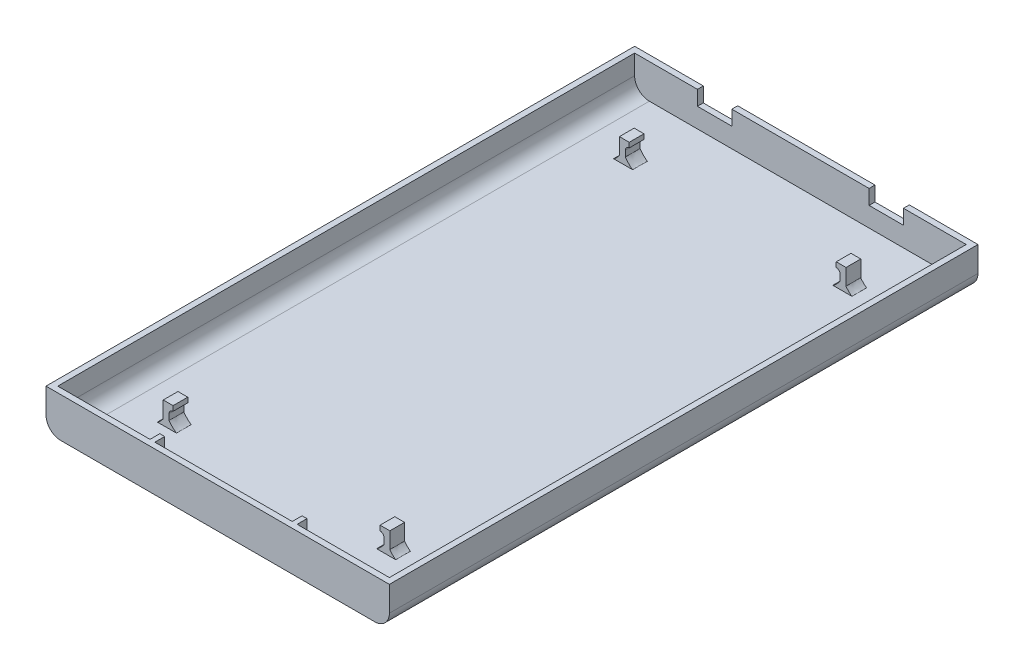
SolidWorks part; units mm, degrees
ref_plane "Front Plane" through (0, 0, 0) normal (0, 0, 1) x (1, 0, 0)
ref_plane "Top Plane" through (0, 0, 0) normal (0, 1, 0) x (1, 0, 0)
ref_plane "Right Plane" through (0, 0, 0) normal (1, 0, 0) x (0, 0, -1)
sketch "Sketch1" plane through (0, 0, 0) normal (0, 1, 0) x (1, 0, 0)
  line L1 (0, 0) -> (70, 0)
  line L2 (0, 0) -> (0, -120)
  line L3 (0, -120) -> (70, -120)
  line L4 (70, 0) -> (70, -120)
  dimension "D1" = 70
  dimension "D2" = 120
extrude "Boss-Extrude1" add sketch "Sketch1" along normal blind 1.1
sketch "Sketch2" plane through (0, 1.1, 0) normal (0, 1, 0) x (1, 0, 0)
  line L0 (70, -120) -> (70, 0) construction
  line L1 (0, -120) -> (70, -120)
  line L2 (0, -120) -> (0, 0)
  line L3 (0, 0) -> (70, 0)
  line L4 (70, -120) -> (70, 0)
  line L5 (1.2, -118.8) -> (1.2, -1.2)
  line L6 (1.2, -1.2) -> (68.8, -1.2)
  line L7 (68.8, -118.8) -> (68.8, -1.2)
  line L8 (1.2, -118.8) -> (68.8, -118.8)
  dimension "D1" = 1.2
extrude "Boss-Extrude2" add sketch "Sketch2" along normal blind 7
sketch "Sketch3" plane through (0, 1.1, 0) normal (0, 1, 0) x (1, 0, 0)
  line L0 (56.9, -15) -> (56.9, -12)
  line L1 (11.9, -15) -> (13.1, -15)
  line L2 (11.9, -15) -> (11.9, -12)
  line L3 (11.9, -12) -> (13.1, -12)
  line L4 (13.1, -15) -> (13.1, -12)
  line L5 (56.9, -15) -> (58.1, -15)
  line L6 (58.1, -15) -> (58.1, -12)
  line L7 (56.9, -12) -> (58.1, -12)
  line L8 (56.9, -108) -> (56.9, -105)
  line L9 (56.9, -108) -> (58.1, -108)
  line L10 (58.1, -108) -> (58.1, -105)
  line L11 (56.9, -105) -> (58.1, -105)
  line L12 (11.9, -108) -> (11.9, -105)
  line L13 (11.9, -108) -> (13.1, -108)
  line L14 (13.1, -108) -> (13.1, -105)
  line L15 (11.9, -105) -> (13.1, -105)
  line L16 (0, 0) -> (0, -120) construction
  line L19 (70, 0) -> (0, 0) construction
  dimension "D3" = 11.9
  dimension "D4" = 1.2
  dimension "D5" = 3
  dimension "D6" = 46.2
  dimension "D7" = 12
  dimension "D1" = 2
  dimension "D2" = 2
extrude "Boss-Extrude3" add sketch "Sketch3" along normal blind 4.5
sketch "Sketch5" plane through (0, 0, 12) normal (0, 0, -1) x (-1, 0, 0)
  line L1 (-56.9, 5.6) -> (-56.1, 5.6)
  line L2 (-56.9, 5.6) -> (-56.9, 4.6)
  line L3 (-56.9, 4.6) -> (-56.1, 4.6)
  line L4 (-56.1, 5.6) -> (-56.1, 4.6)
  line L5 (-13.1, 5.6) -> (-13.9, 5.6)
  line L6 (-13.1, 5.6) -> (-13.1, 4.6)
  line L7 (-13.1, 4.6) -> (-13.9, 4.6)
  line L8 (-13.9, 5.6) -> (-13.9, 4.6)
  dimension "D1" = 0.8
  dimension "D2" = 0.8
  dimension "D3" = 1
  dimension "D4" = 1
extrude "Boss-Extrude4" add sketch "Sketch5" against normal blind 3
sketch "Sketch6" plane through (0, 0, 105) normal (0, 0, -1) x (-1, 0, 0)
  line L1 (-56.9, 5.6) -> (-56.1, 5.6)
  line L2 (-56.9, 5.6) -> (-56.9, 4.6)
  line L3 (-56.9, 4.6) -> (-56.1, 4.6)
  line L4 (-56.1, 5.6) -> (-56.1, 4.6)
  line L5 (-13.1, 5.6) -> (-13.9, 5.6)
  line L6 (-13.1, 5.6) -> (-13.1, 4.6)
  line L7 (-13.1, 4.6) -> (-13.9, 4.6)
  line L8 (-13.9, 5.6) -> (-13.9, 4.6)
  dimension "D1" = 0.8
  dimension "D2" = 0.8
  dimension "D3" = 1
  dimension "D4" = 1
extrude "Boss-Extrude5" add sketch "Sketch6" against normal blind 3
sketch "Sketch7" plane through (0, 8.1, 0) normal (0, 1, 0) x (1, 0, 0)
  line L0 (68.8, -1.2) -> (1.2, -1.2) construction
  line L1 (56, -1.2) -> (49, -1.2)
  line L2 (56, -1.2) -> (56, 0)
  line L3 (56, 0) -> (49, 0)
  line L4 (49, -1.2) -> (49, 0)
  line L5 (70, 0) -> (0, 0) construction
  line L6 (70, -120) -> (70, 0) construction
  line L7 (14, -1.2) -> (21, -1.2)
  line L8 (14, -1.2) -> (14, 0)
  line L9 (14, 0) -> (21, 0)
  line L10 (21, -1.2) -> (21, 0)
  line L11 (0, 0) -> (0, -120) construction
  dimension "D1" = 14
  dimension "D2" = 14
  dimension "D3" = 7
  dimension "D4" = 7
extrude "Cut-Extrude1" cut sketch "Sketch7" against normal blind 3
sketch "Sketch8" plane through (0, 0, 118.8) normal (0, 0, -1) x (-1, 0, 0)
  line L0 (-1.2, 8.1) -> (-68.8, 8.1) construction
  line L1 (-49, 8.1) -> (-50, 8.1)
  line L2 (-49, 8.1) -> (-49, 1.1)
  line L3 (-49, 1.1) -> (-50, 1.1)
  line L4 (-50, 8.1) -> (-50, 1.1)
  line L5 (-1.2, 1.1) -> (-68.8, 1.1) construction
  line L6 (-70, 8.1) -> (-70, 0) construction
  line L7 (-21, 8.1) -> (-20, 8.1)
  line L8 (-21, 8.1) -> (-21, 1.1)
  line L9 (-21, 1.1) -> (-20, 1.1)
  line L10 (-20, 8.1) -> (-20, 1.1)
  line L11 (0, 8.1) -> (0, 0) construction
  dimension "D1" = 1
  dimension "D2" = 1
  dimension "D3" = 20
  dimension "D4" = 20
extrude "Boss-Extrude6" add sketch "Sketch8" along normal blind 2
fillet "Fillet1" radius 1.5 4 edges at (56.9, 1.1, 13.5) (56.9, 1.1, 106.5) (13.1, 1.1, 13.5) (13.1, 1.1, 106.5) conic rho 0.1
fillet "Fillet2" radius 1.2 4 edges at (11.9, 1.1, 13.5) (58.1, 1.1, 13.5) (58.1, 1.1, 106.5) (11.9, 1.1, 106.5) conic rho 0.1
fillet "Fillet3" radius 0.8 4 edges at (56.9, 4.6, 106.5) (56.9, 4.6, 13.5) (13.1, 4.6, 13.5) (13.1, 4.6, 106.5)
fillet "Fillet4" radius 3 4 edges at (0, 0, 60) (70, 0, 60) (68.8, 1.1, 60) (1.2, 1.1, 60)
equation "\"D3@Sketch3\"=(\"D1@Sketch1\"-45-1.2)/2"
equation "\"D7@Sketch3\"=(\"D2@Sketch1\"-93-3)/2"
